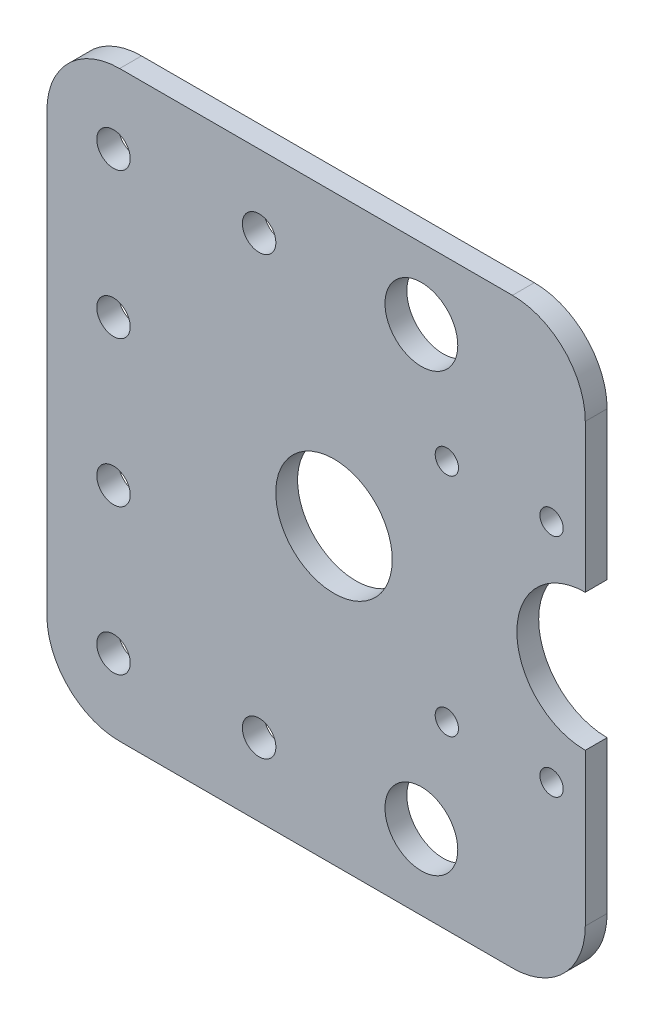
SolidWorks part; units mm, degrees
ref_plane "Front Plane" through (0, 0, 0) normal (0, 0, 1) x (1, 0, 0)
ref_plane "Top Plane" through (0, 0, 0) normal (0, 1, 0) x (1, 0, 0)
ref_plane "Right Plane" through (0, 0, 0) normal (1, 0, 0) x (0, 0, -1)
sketch "Sketch1" plane through (0, 0, 0) normal (0, 0, 1) x (1, 0, 0)
  line L0 (157.9607, -71.8662) -> (170.4739, -71.8662)
  line L1 (116.5258, -71.8662) -> (157.9607, -71.8662)
  line L2 (106.5258, -81.8662) -> (106.5258, -141.8968)
  line L3 (116.5258, -151.8968) -> (157.9607, -151.8968)
  line L4 (180.4739, -81.8662) -> (180.4739, -102.194)
  line L5 (145.9607, -111.5917) -> (157.9607, -111.5917) construction
  line L6 (157.9607, -111.5917) -> (157.9607, -81.5917) construction
  line L7 (157.9607, -111.5917) -> (157.9607, -141.5917) construction
  line L8 (170.4739, -151.8968) -> (157.9607, -151.8968)
  line L9 (180.4739, -120.9895) -> (180.4739, -141.8968)
  circle A0 centre (115.6746, -101.8662) radius 2.3
  circle A1 centre (115.6746, -121.8662) radius 2.3
  circle A2 centre (135.6746, -141.8662) radius 2.3
  circle A3 centre (135.6746, -81.8662) radius 2.3
  circle A4 centre (115.6746, -81.8662) radius 2.3
  circle A5 centre (115.6746, -141.8662) radius 2.3
  circle A6 centre (161.4607, -96.1142) radius 1.6
  circle A7 centre (161.4607, -127.1142) radius 1.6
  arc A8 (180.4739, -102.194) -> (180.4739, -120.9895) centre (180.4739, -111.5917) ccw
  arc A9 (180.4739, -141.8968) -> (170.4739, -151.8968) centre (170.4739, -141.8968) cw
  circle A10 centre (145.9607, -111.5917) radius 8
  arc A11 (180.4739, -81.8662) -> (170.4739, -71.8662) centre (170.4739, -81.8662) ccw
  circle A12 centre (175.8433, -96.1142) radius 1.6
  arc A13 (106.5258, -141.8968) -> (116.5258, -151.8968) centre (116.5258, -141.8968) ccw
  arc A14 (116.5258, -71.8662) -> (106.5258, -81.8662) centre (116.5258, -81.8662) ccw
  circle A15 centre (157.9607, -81.5917) radius 5
  circle A16 centre (157.9607, -141.5917) radius 5
  circle A17 centre (175.8433, -127.1142) radius 1.6
  point P47 (106.5258, -71.8662)
  dimension "D1" = 10
  dimension "D4" = 12
  dimension "D2" = 30
  dimension "D3" = 30
extrude "Boss-Extrude1" add sketch "Sketch1" along normal blind 3
